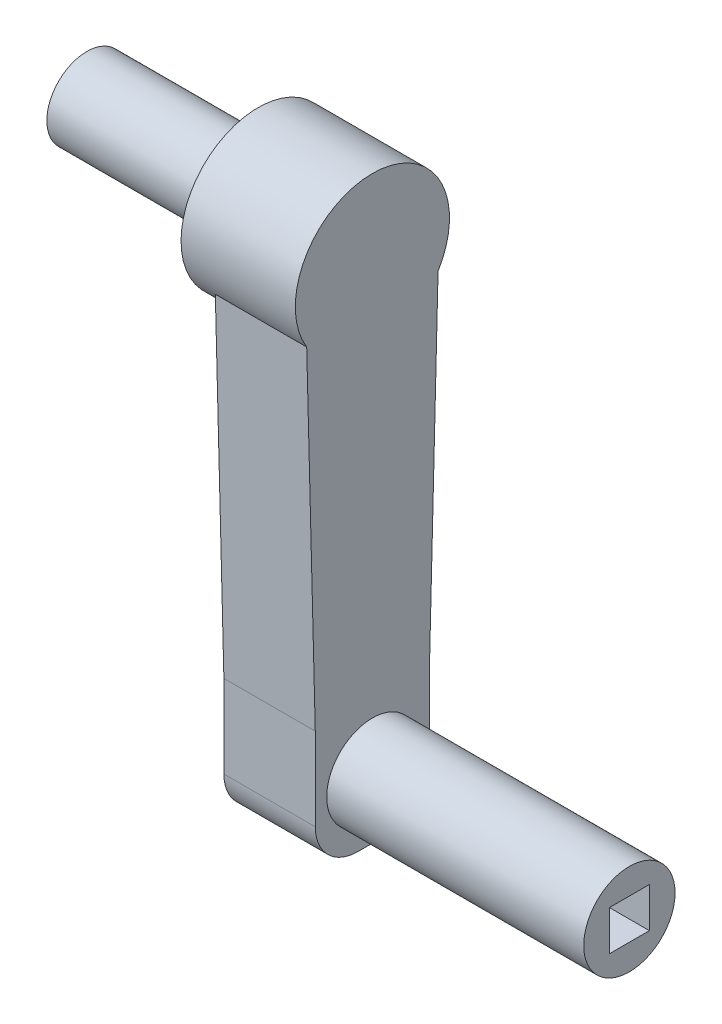
SolidWorks part; units mm, degrees
note: The reader was unsure of these and kept them because the rebuilt part matched: shared geometry of "Esquisse1<5>", "Esquisse1<6>".
material "Commercialement pur CP-Ti UNS R50400 (SS)"
ref_plane "Plan de face" through (0, 0, 0) normal (0, 0, 1) x (1, 0, 0)
ref_plane "Plan de dessus" through (0, 0, 0) normal (0, 1, 0) x (1, 0, 0)
ref_plane "Plan de droite" through (0, 0, 0) normal (1, 0, 0) x (0, 0, -1)
sketch "Esquisse1" plane through (0, 0, 0) normal (1, 0, 0) x (0, 0, -1)
  line L0 (-135, 0) -> (135, 0) construction
  line L1 (-115, -70.7107) -> (115, -70.7107)
  line L2 (-97.2034, -770.7107) -> (97.2034, -770.7107)
  line L3 (97.2034, -770.7107) -> (115, -70.7107)
  line L4 (-115, -70.7107) -> (-97.2034, -770.7107)
  line L5 (0, -70.7107) -> (0, -770.7107) construction
  line L7 (25, -880.7107) -> (-25, -880.7107)
  line L8 (100, -805.7107) -> (100, -660.7107)
  line L9 (100, -660.7107) -> (-100, -660.7107)
  line L10 (-100, -805.7107) -> (-100, -660.7107)
  line L11 (100, -880.7107) -> (-100, -660.7107) construction
  line L12 (100, -660.7107) -> (-100, -880.7107) construction
  circle A0 centre (0, 0) radius 70
  circle A1 centre (0, 0) radius 135
  circle A2 centre (0, -770.7107) radius 80
  arc A3 (25, -880.7107) -> (100, -805.7107) centre (25, -805.7107) ccw
  arc A4 (-25, -880.7107) -> (-100, -805.7107) centre (-25, -805.7107) cw
  dimension "D1" = 140
  dimension "D2" = 270
  dimension "D7" = 160
  dimension "D8" = 75
  dimension "D3" = 230
  dimension "D4" = 700
  dimension "D5" = 220
  dimension "D6" = 200
extrude "Boss.-Extru.1" add sketch "Esquisse1" along normal blind 200 contours L1 A1 A0 | L1 A1 A0 | A1 L4 L9 L3 | A2 L2 L3 L9 L4 | A4 L7 A3 L8 L3 L2 A2 L4 L10
extrude "Boss.-Extru.3" add sketch "Esquisse1<5>" along normal blind 650 contours L2 A2 | L2 A2
sketch "Esquisse1<5>" plane through (0, 0, 0) normal (1, 0, 0) x (0, 0, -1) same geometry as "Esquisse1"
sketch "Esquisse4" plane through (650, 0, 0) normal (1, 0, 0) x (0, 0, -1)
  line L1 (-35, -805.7107) -> (35, -805.7107)
  line L2 (-35, -805.7107) -> (-35, -735.7107)
  line L3 (-35, -735.7107) -> (35, -735.7107)
  line L4 (35, -805.7107) -> (35, -735.7107)
  line L5 (-35, -805.7107) -> (35, -735.7107) construction
  line L6 (-35, -735.7107) -> (35, -805.7107) construction
  point P0 (0, -770.7107)
  dimension "D1" = 70
  dimension "D2" = 70
extrude "Enlèv. mat.-Extru.4" cut sketch "Esquisse4" against normal blind 100
extrude "Boss.-Extru.4" add sketch "Esquisse1<6>" against normal blind 300 separate body contours A0
sketch "Esquisse1<6>" plane through (0, 0, 0) normal (1, 0, 0) x (0, 0, -1) same geometry as "Esquisse1"
chamfer "Chanfrein1" distance 40 angle 45 5 edges at (0, -733.2107, -100) (0, -733.2107, 100) (0, -858.7437, -78.033) (0, -858.7437, 78.033) (0, -880.7107, 0)
